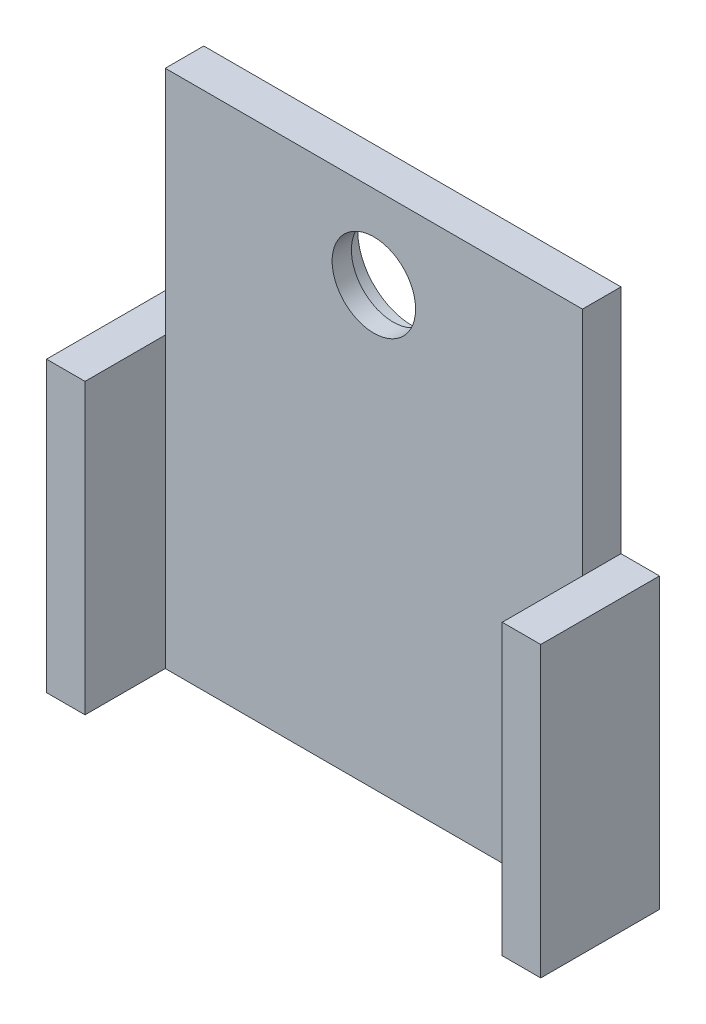
SolidWorks part; units mm, degrees
ref_plane "Plano frontal" through (0, 0, 0) normal (0, 0, 1) x (1, 0, 0)
ref_plane "Plano superior" through (0, 0, 0) normal (0, 1, 0) x (1, 0, 0)
ref_plane "Plano direito" through (0, 0, 0) normal (1, 0, 0) x (0, 0, -1)
sketch "Esboço1" plane through (0, 0, 0) normal (0, 0, 1) x (1, 0, 0)
  line L0 (16, -4.75) -> (16, -11.25) construction
  line L1 (16.25, -11.25) -> (-16.25, -11.25)
  line L2 (16.25, -11.25) -> (16.25, 29.25)
  line L3 (16.25, 29.25) -> (-16.25, 29.25)
  line L4 (-16.25, -11.25) -> (-16.25, 29.25)
  line L5 (-16, -11.25) -> (-16, -4.75) construction
  line L8 (-14.5, -11.25) -> (-10.25, -11.25) construction
  line L10 (-11, 29.25) -> (11, 29.25) construction
  dimension "D1" = 0.25
  dimension "D2" = 0.25
extrude "Ressalto-extrusão1" add sketch "Esboço1" against normal blind 3
sketch "Esboço4" plane through (-16.25, 0, 0) normal (-1, 0, 0) x (0, 0, 1)
  line L1 (-3, -11.25) -> (6.25, -11.25)
  line L2 (-3, -11.25) -> (-3, 11.25)
  line L3 (-3, 11.25) -> (6.25, 11.25)
  line L4 (6.25, -11.25) -> (6.25, 11.25)
  line L5 (6.5, -8.3463) -> (6.5, 13.8) construction
  line L6 (28.75, 11.25) -> (69.25, 11.25) construction
  dimension "D1" = 0.25
extrude "Ressalto-extrusão2" add sketch "Esboço4" along normal blind 3
mirror "Espelhar1" about plane through (0, 0, 0) normal (1, 0, 0) of "Ressalto-extrusão2"
sketch "Esboço5" plane through (0, 0, -3) normal (0, 0, -1) x (-1, 0, 0)
  circle A3 centre (0, 22.75) radius 4.25
  circle A4 centre (0, 22.75) radius 4 construction
  dimension "D1" = 0.25
extrude "Corte-extrusão1" cut sketch "Esboço5" against normal offset from surface (1.5 mm away) 1.5 up to face at (0, 9.75, 0)
sketch "Esboço6" plane through (0, 0, -3) normal (0, 0, -1) x (-1, 0, 0)
  circle A0 centre (0, 22.75) radius 3.25 construction
  circle A1 centre (0, 22.75) radius 3.25
extrude "Corte-extrusão2" cut sketch "Esboço6" against normal through all
